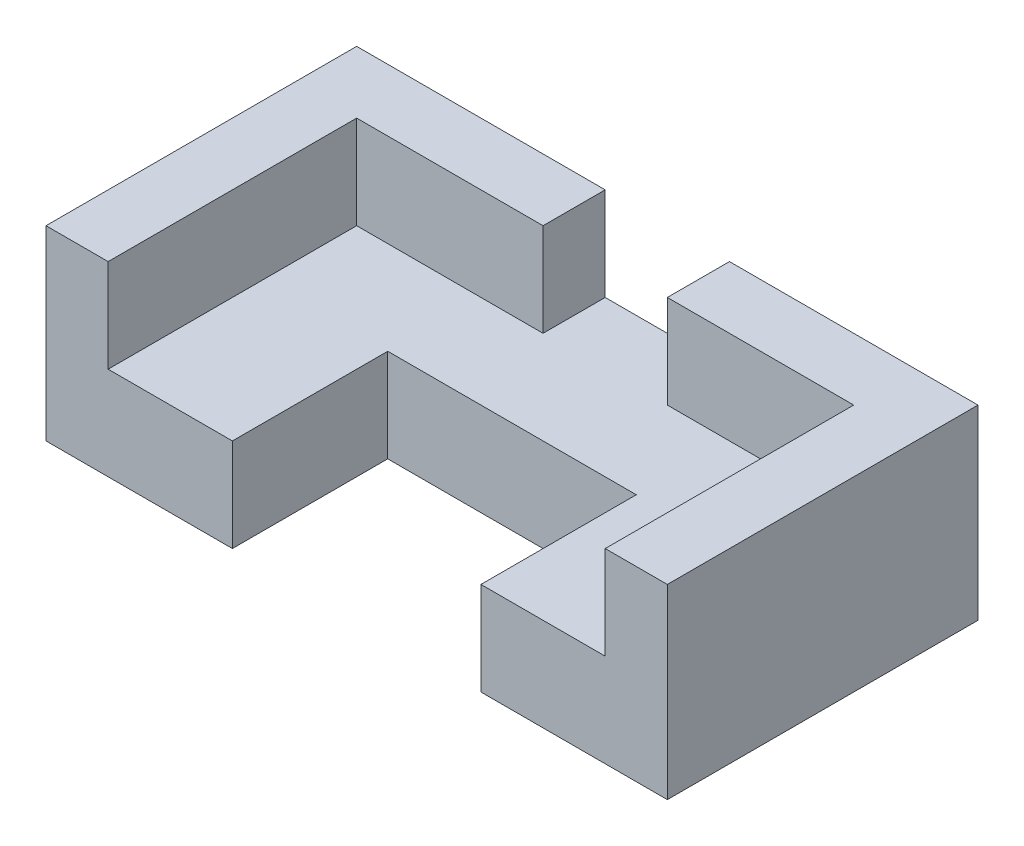
SolidWorks part; units mm, degrees
ref_plane "Front Plane" through (0, 0, 0) normal (0, 0, 1) x (1, 0, 0)
ref_plane "Top Plane" through (0, 0, 0) normal (0, 1, 0) x (1, 0, 0)
ref_plane "Right Plane" through (0, 0, 0) normal (1, 0, 0) x (0, 0, -1)
sketch "Sketch1" plane through (0, 0, 0) normal (0, 0, 1) x (1, 0, 0)
  line L0 (10, 30) -> (10, 15)
  line L1 (0, 0) -> (100, 0)
  line L2 (0, 0) -> (0, 30)
  line L3 (0, 30) -> (100, 30)
  line L4 (100, 0) -> (100, 30)
  line L5 (10, 15) -> (90, 15)
  line L6 (90, 15) -> (90, 30)
  line L7 (30, 15) -> (30, 0)
  line L8 (70, 15) -> (70, 0)
  line L9 (40, 15) -> (40, 30)
  line L10 (60, 30) -> (60, 15)
  point P17 (-59.3427, 78.3239)
  point P18 (0, 0)
  dimension "D1" = 100
  dimension "D2" = 30
  dimension "D3" = 40
  dimension "D4" = 30
  dimension "D5" = 15
  dimension "D6" = 10
  dimension "D7" = 10
  dimension "D8" = 20
  dimension "D9" = 40
extrude "Boss-Extrude1" add sketch "Sketch1" along normal blind 50 contours L7 L5 L0 L3 L2 L1 | L5 L8 L1 L4 L3 L6 region at (12.5, 11.25, 0) region at (87.5, 11.25, 0)
extrude "Boss-Extrude2" add sketch "Sketch1<3>" along normal blind 25 contours L8 L5 L7 L1 region at (50, 7.5, 0)
sketch "Sketch1<3>" plane through (0, 0, 0) normal (0, 0, 1) x (1, 0, 0) same geometry as "Sketch1"
extrude "Boss-Extrude3" add sketch "Sketch1<4>" along normal blind 10 contours L5 L9 L3 L0 | L3 L10 L5 L6 region at (25, 22.5, 0) region at (75, 22.5, 0)
sketch "Sketch1<4>" plane through (0, 0, 0) normal (0, 0, 1) x (1, 0, 0) same geometry as "Sketch1"
